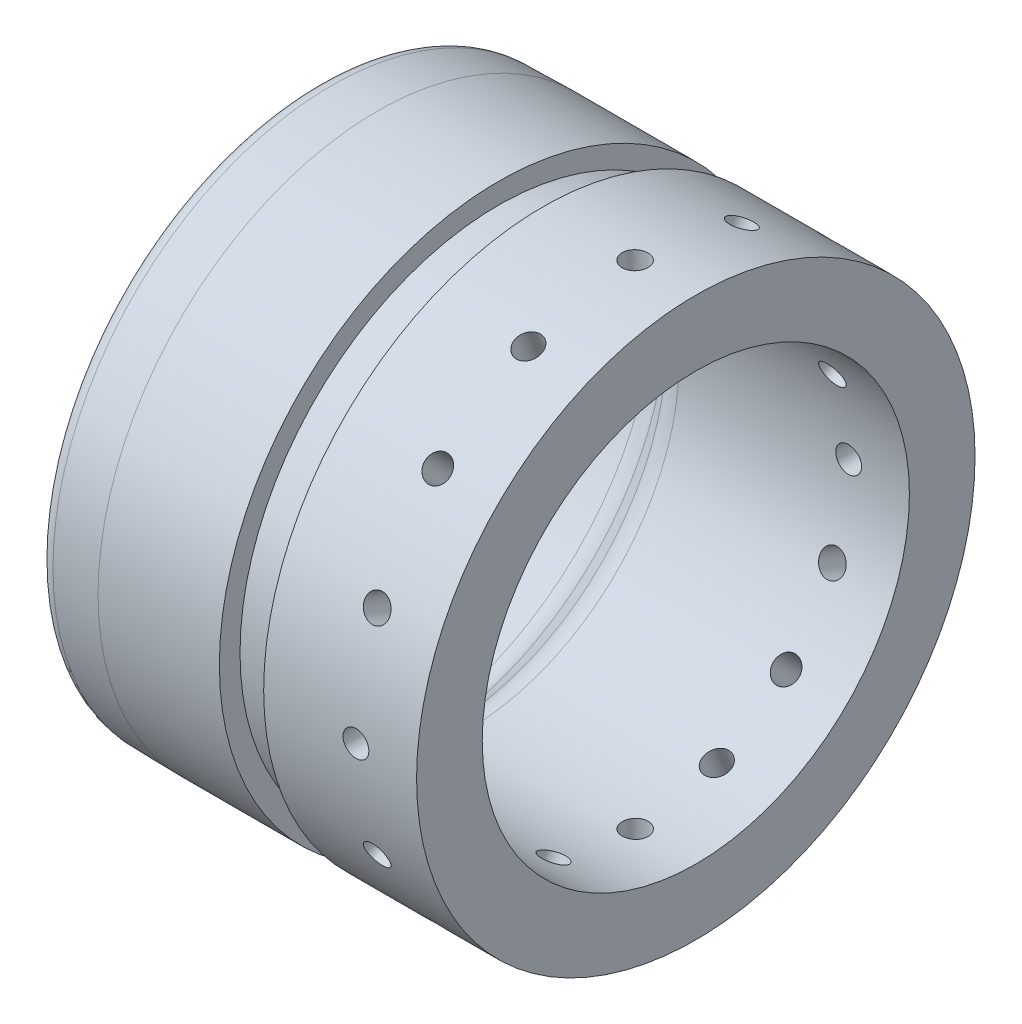
SolidWorks part; units mm, degrees
material "6061-T6 (SS)"
ref_plane "Front Plane" through (0, 0, 0) normal (0, 0, 1) x (1, 0, 0)
ref_plane "Top Plane" through (0, 0, 0) normal (0, 1, 0) x (1, 0, 0)
ref_plane "Right Plane" through (0, 0, 0) normal (1, 0, 0) x (0, 0, -1)
sketch "Sketch1" plane through (0, 0, 0) normal (0, 0, 1) x (1, 0, 0)
  line L12 (0.0186, 58.9466) -> (98.3939, 58.9466) construction
  line L19 (-3.9714, 6.5774) -> (1.8338, 12.3827)
  line L28 (6.324, 14.2426) -> (54.4937, 14.2426)
  line L29 (54.4937, 0.5012) -> (54.4937, 14.2426)
  line L30 (13.2187, 0.5012) -> (13.2187, 4.8192)
  line L31 (13.2187, 4.8192) -> (22.4897, 4.8192)
  line L32 (22.4897, 4.8192) -> (22.4897, 0.5012)
  line L33 (22.4897, 0.5012) -> (54.4937, 0.5012)
  line L34 (-24.8999, 0.5012) -> (13.2187, 0.5012)
  line L35 (-24.8999, 0.5012) -> (-12.1813, 0.5012)
  line L36 (-12.1813, 0.5012) -> (-24.8999, 0.7232)
  line L38 (-24.8999, 4.7176) -> (-8.4616, 4.7176)
  line L39 (-24.8999, 4.7176) -> (-24.8999, 0.7232)
  line L40 (-24.8999, 0.7232) -> (-24.8999, 0.5012)
  arc A0 (-3.9714, 6.5774) -> (-8.4616, 4.7176) centre (-8.4616, 11.0676) cw
  arc A1 (6.324, 14.2426) -> (1.8338, 12.3827) centre (6.324, 7.8926) ccw
  point P8 (-5.8499, 4.2164)
  point P22 (3.6751, 13.7414)
  dimension "D15" = 4.7176
  dimension "D16" = 4.8192
  dimension "D8" = 3.9714
  dimension "D9" = 5.8499
  dimension "D1" = 6.35
  dimension "D3" = 3.6751
  dimension "D2" = 1.8338
  dimension "D4" = 6.324
  dimension "D5" = 13.2187
  dimension "D6" = 22.4897
  dimension "D7" = 54.4937
  dimension "D10" = 0.5012
  dimension "D11" = 12.1813
  dimension "D12" = 24.8999
  dimension "D13" = 0.7232
  dimension "D14" = 4.2164
  dimension "D21" = 13.7414
  dimension "D23" = 58.9466
revolve "Revolve1" add sketch "Sketch1" angle 360 about L12 region at (22.3214, 6.9343, 0)
ref_plane "Tap Reference Plane" through (0, 0, -58.4454) normal (0, 0, -1) x (-1, 0, 0)
sketch "Tap Reference" plane through (0, 0, -58.4454) normal (0, 0, -1) x (-1, 0, 0)
  line L0 (-54.4937, 58.9466) -> (-41.7937, 58.9466)
  line L2 (-54.4937, 117.392) -> (-54.4937, 0.5012) construction
  point P5 (-41.7937, 58.9466)
hole_wizard "Tap Drill for 1/4-28 Tap1" positions "Sketch4" profile "Sketch6" hole size "1/4-28" standard "ANSI Inch" end condition through all
sketch "Sketch4" plane through (0, 0, -58.4454) normal (0, 0, -1) x (-1, 0, 0)
  point P0 (-41.7937, 58.9466)
sketch "Sketch6" plane through (41.7937, 58.9466, -58.4454) normal (1, 0, 0) x (0, 1, 0)
  line L0 (0, 0) -> (0, 116.8908)
  line L1 (0, 116.8908) -> (2.7051, 116.8908)
  line L2 (2.7051, 116.8908) -> (2.7051, 0)
  line L5 (2.7051, 0) -> (0, 0)
  line L11 (0, -6.35) -> (0, 107.95) construction
  dimension "Thru Hole Dia." = 5.4102
  dimension "Thru Hole Depth" = 116.8908
pattern_circular "Tap Pattern" count 16 over 360 about axis through (0.0186, 58.9466, 0) along (1, 0, 0) of "Tap Drill for 1/4-28 Tap1" reverse direction yes
fillet "Fillet1" radius 3.175 1 edges at (-24.8999, 58.9466, 58.2234)
ref_plane "Plane1" through (54.4937, 0, 0) normal (1, 0, 0) x (0, 0, -1)
ref_plane "Plane2" through (-24.8999, 0, 0) normal (-1, 0, 0) x (0, 0, 1)
